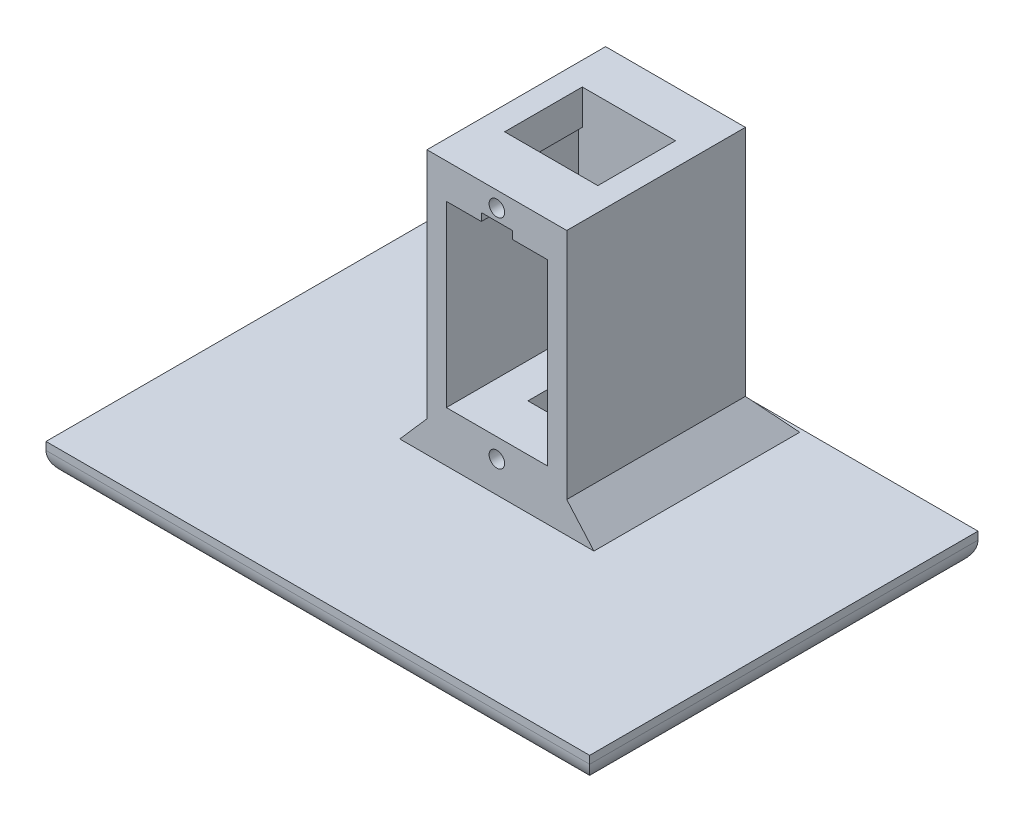
SolidWorks part; units mm, degrees
note: '?' marks a value the reader was unsure of.
ref_plane "Front Plane" through (0, 0, 0) normal (0, 0, 1) x (1, 0, 0)
ref_plane "Top Plane" through (0, 0, 0) normal (0, 1, 0) x (1, 0, 0)
ref_plane "Right Plane" through (0, 0, 0) normal (1, 0, 0) x (0, 0, -1)
sketch "Sketch1" plane through (0, -109.5426, 0) normal (0, -1, 0) x (1, 0, 0)
  line L0 (5.4838, -24.3761) -> (5.4838, -44.3761)
  line L1 (5.4838, -44.3761) -> (23.4838, -44.3761)
  line L2 (8.4838, -24.3761) -> (20.4838, -24.3761)
  line L3 (8.4838, -24.3761) -> (8.4838, -41.3761)
  line L4 (8.4838, -41.3761) -> (20.4838, -41.3761)
  line L5 (20.4838, -24.3761) -> (20.4838, -41.3761)
  line L6 (23.4838, -24.3761) -> (23.4838, -44.3761)
  line L7 (5.4838, -24.3761) -> (8.4838, -24.3761)
  line L8 (23.4838, -24.3761) -> (20.4838, -24.3761)
  line M6 (8.4838, -24.3761) -> (8.4838, -41.3761)
  line M7 (8.4838, -41.3761) -> (20.4838, -41.3761)
  line M8 (20.4838, -41.3761) -> (20.4838, -24.3761)
  dimension "D1" = 3
extrude "Boss-Extrude1" add sketch "Sketch1" against normal up to vertex (22 mm away) contours L6 L8 L7 L0 L1 M8 M7 M6
sketch "Sketch2" plane through (0, -109.5426, 0) normal (0, -1, 0) x (1, 0, 0)
  line L0 (23.4838, -24.3761) -> (23.4838, -44.3761) construction
  line L1 (5.4838, -24.3761) -> (23.4838, -24.3761)
  line L2 (5.4838, -24.3761) -> (5.4838, -44.3761)
  line L3 (5.4838, -44.3761) -> (23.4838, -44.3761)
  line L4 (23.4838, -24.3761) -> (23.4838, -44.3761)
extrude "Boss-Extrude2" add sketch "Sketch2" along normal blind 7
sketch "Sketch3" plane through (0, -116.5426, 0) normal (0, -1, 0) x (1, 0, 0)
  line L0 (5.4838, -26.3256) -> (23.4838, -26.3256) construction
  line L3 (5.4838, -24.3761) -> (5.4838, -44.3761) construction
  line L4 (23.4838, -44.3761) -> (23.4838, -24.3761) construction
  line L5 (5.4838, -26.3256) -> (5.4838, -24.3761) construction
  line L7 (-20.5162, -51.3256) -> (49.4838, -51.3256)
  line L8 (-20.5162, -51.3256) -> (-20.5162, -1.3256)
  line L9 (-20.5162, -1.3256) -> (49.4838, -1.3256)
  line L10 (49.4838, -51.3256) -> (49.4838, -1.3256)
  line L11 (14.4838, -1.3256) -> (14.4838, -51.3256) construction
  line L12 (-20.5162, -26.3256) -> (49.4838, -26.3256) construction
  point P12 (14.4838, -26.3256)
  dimension "D1" = 50
  dimension "D2" = 70
  dimension "D3" = 1.9496
  dimension "D4" = 18
extrude "Boss-Extrude3" add sketch "Sketch3" along normal blind 4
sketch "Sketch31" plane through (0, -116.5426, 0) normal (0, 1, 0) x (1, 0, 0)
  line L0 (23.4838, 44.3761) -> (23.4838, 47.3761) construction
  line L2 (5.4838, 44.3761) -> (23.4838, 44.3761)
  line L3 (5.4838, 44.3761) -> (5.4838, 47.3761)
  line L4 (5.4838, 47.3761) -> (23.4838, 47.3761)
  line L5 (23.4838, 44.3761) -> (23.4838, 47.3761)
  dimension "D1" = 3
  dimension "D4" = 18
extrude "Boss-Extrude7" add sketch "Sketch31" along normal blind 34
sketch "Sketch4" plane through (0, 0, -51.3256) normal (0, 0, -1) x (-1, 0, 0)
  line L0 (-49.4838, -117.5426) -> (-49.4838, -120.5426)
  line L1 (-49.4838, -116.5426) -> (20.5162, -116.5426) construction
  line L2 (-49.4838, -116.5426) -> (-49.4838, -117.5426) construction
  line L3 (-46.4838, -120.5426) -> (17.5162, -120.5426) construction
  line L4 (20.5162, -116.5426) -> (20.5162, -117.5426) construction
  line L5 (-49.4838, -120.5426) -> (-46.4838, -120.5426)
  line L6 (17.5162, -120.5426) -> (20.5162, -120.5426)
  line L7 (20.5162, -120.5426) -> (20.5162, -117.5426)
  arc A0 (-49.4838, -117.5426) -> (-46.4838, -120.5426) centre (-46.4838, -117.5426) ccw
  arc A1 (20.5162, -117.5426) -> (17.5162, -120.5426) centre (17.5162, -117.5426) cw
  point P10 (20.5162, -120.5426)
  dimension "D1" = 3
  dimension "D2" = 3
extrude "Cut-Extrude1" cut sketch "Sketch4" against normal up to next
sketch "Sketch6" plane through (-20.5162, 0, 0) normal (-1, 0, 0) x (0, 0, 1)
  line L0 (-1.3256, -120.5426) -> (-1.3256, -117.5426) construction
  line L1 (-51.3256, -116.5426) -> (-1.3256, -116.5426) construction
  line L2 (-51.3256, -116.5426) -> (-51.3256, -117.5426) construction
  line L3 (-48.3256, -120.5426) -> (-4.3256, -120.5426) construction
  line L4 (-1.3256, -116.5426) -> (-1.3256, -117.5426) construction
  line L5 (-1.3256, -120.5426) -> (-51.3256, -120.5426) construction
  line L6 (-4.3256, -117.5426) -> (-4.3256, -116.5426) construction
  line L7 (-4.3256, -116.5426) -> (-1.3256, -116.5426) construction
  arc A0 (-4.3256, -120.5426) -> (-1.3256, -117.5426) centre (-4.3256, -117.5426) ccw
  arc A1 (-51.3256, -117.5426) -> (-48.3256, -120.5426) centre (-48.3256, -117.5426) ccw
  point P11 (-1.3256, -120.5426)
  dimension "D1" = 3
  dimension "D2" = 1
extrude "Cut-Extrude-Thin1" cut sketch "Sketch6" against normal up to next thin
sketch "Sketch7" plane through (0, -116.5426, 0) normal (0, 1, 0) x (1, 0, 0)
  line L0 (23.4838, 24.3761) -> (23.4838, 44.3761) construction
  line L1 (5.4838, 47.3761) -> (23.4838, 47.3761)
  line L2 (5.4838, 47.3761) -> (5.4838, 24.3761)
  line L3 (5.4838, 24.3761) -> (23.4838, 24.3761)
  line L4 (23.4838, 47.3761) -> (23.4838, 24.3761)
  line L5 (1.9838, 50.8761) -> (1.9838, 20.8761)
  line L6 (1.9838, 20.8761) -> (26.9838, 20.8761)
  line L7 (26.9838, 50.8761) -> (26.9838, 20.8761)
  line L8 (1.9838, 50.8761) -> (26.9838, 50.8761)
  dimension "D1" = 23
  dimension "D2" = 3.5
ref_plane "Plane1" through (0, -112.5426, 0) normal (0, 1, 0) x (1, 0, 0)
sketch "Sketch8" plane through (0, -112.5426, 0) normal (0, 1, 0) x (1, 0, 0)
  line L1 (23.4838, 47.3761) -> (23.4838, 24.3761) construction
  line L2 (5.4838, 24.3761) -> (23.4838, 24.3761) construction
  line L3 (5.4838, 47.3761) -> (5.4838, 24.3761) construction
  line L4 (5.4838, 47.3761) -> (23.4838, 47.3761)
  line L5 (23.4838, 47.3761) -> (23.4838, 24.3761)
  line L6 (5.4838, 24.3761) -> (23.4838, 24.3761)
  line L7 (5.4838, 47.3761) -> (5.4838, 24.3761)
  dimension "D1" = 23
  dimension "D2" = 18
loft "Loft2" add profiles "Sketch8" section "Sketch7" section "Sketch8"
sketch "Sketch9" plane through (5.4838, 0, 0) normal (-1, 0, 0) x (0, 0, 1)
  line L0 (-24.3761, -112.5426) -> (-24.3761, -116.5426)
  line L1 (-1.3256, -116.5426) -> (-51.3256, -116.5426) construction
  line L2 (-24.3761, -116.5426) -> (-20.8761, -116.5426)
  line L3 (-20.8761, -116.5426) -> (-24.3761, -112.5426) construction
  line L4 (-20.8761, -116.5426) -> (-24.3761, -112.5426)
  dimension "D1" = 3.5
  dimension "D2" = 4
extrude "Cut-Extrude2" cut sketch "Sketch9" against normal through all both and the other way through all
sketch "Sketch10" plane through (0, 0, -24.3761) normal (0, 0, 1) x (1, 0, 0)
  circle A0 centre (14.4838, -112.5426) radius 1
  dimension "D1" = 2
extrude "Cut-Extrude3" cut sketch "Sketch10" against normal blind 10
sketch "Sketch11" plane through (0, 0, -24.3761) normal (0, 0, 1) x (1, 0, 0)
  line L0 (20.4838, -109.5426) -> (8.4838, -109.5426) construction
  line L1 (12.4838, -114.5426) -> (16.4838, -114.5426)
  line L2 (12.4838, -114.5426) -> (12.4838, -109.5426)
  line L3 (12.4838, -109.5426) -> (16.4838, -109.5426)
  line L4 (16.4838, -114.5426) -> (16.4838, -109.5426)
  line L5 (14.4838, -109.5426) -> (14.4838, -114.5426) construction
  point P0 (14.4838, -112.5426)
  dimension "D1" = 5
  dimension "D2" = 4
ref_plane "Plane2" through (0, 0, -34.3761) normal (0, 0, 1) x (1, 0, 0)
sketch "Sketch12" plane through (0, 0, -34.3761) normal (0, 0, 1) x (1, 0, 0)
  line L0 (12.4838, -114.5426) -> (16.4838, -114.5426) construction
  line L1 (14.4838, -109.5426) -> (14.4838, -114.5426) construction
  line L2 (12.4838, -114.5426) -> (12.4838, -109.5426) construction
  line L3 (12.4838, -109.5426) -> (16.4838, -109.5426) construction
  line L4 (16.4838, -114.5426) -> (16.4838, -109.5426) construction
  line L5 (12.4838, -114.5426) -> (16.4838, -114.5426)
  line L6 (14.4838, -109.5426) -> (14.4838, -114.5426) construction
  line L7 (12.4838, -114.5426) -> (12.4838, -109.5426)
  line L8 (12.4838, -109.5426) -> (16.4838, -109.5426)
  line L9 (16.4838, -114.5426) -> (16.4838, -109.5426)
extrude "Cut-Extrude4" cut sketch "Sketch12" along normal blind 4
sketch "Sketch13" plane through (0, -87.5426, 0) normal (0, 1, 0) x (1, 0, 0)
  line L2 (5.4838, 47.3761) -> (23.4838, 47.3761)
  line L3 (5.4838, 47.3761) -> (5.4838, 24.3761)
  line L4 (5.4838, 24.3761) -> (23.4838, 24.3761)
  line L5 (23.4838, 47.3761) -> (23.4838, 24.3761)
extrude "Boss-Extrude4" add sketch "Sketch13" along normal blind 5
sketch "Sketch14" plane through (0, 0, -24.3761) normal (0, 0, 1) x (1, 0, 0)
  circle A0 centre (14.4838, -84.5426) radius 1
  dimension "D1" = 2
extrude "Cut-Extrude5" cut sketch "Sketch14" against normal blind 10
sketch "Sketch16" plane through (0, -82.5426, 0) normal (0, 1, 0) x (1, 0, 0)
  line L2 (5.4838, 41.3761) -> (23.4838, 41.3761) construction
  line L3 (5.4838, 47.3761) -> (5.4838, 24.3761) construction
  line L4 (23.4838, 24.3761) -> (23.4838, 47.3761) construction
  line L5 (14.4838, 41.3761) -> (8.4838, 41.3761)
  line L6 (8.4838, 41.3761) -> (8.4838, 31.3761)
  line L7 (8.4838, 31.3761) -> (20.4838, 31.3761)
  line L8 (20.4838, 31.3761) -> (20.4838, 41.3761)
  line L9 (20.4838, 41.3761) -> (14.4838, 41.3761)
  line L10 (23.4838, 41.3761) -> (20.4838, 41.3761) construction
  line L11 (14.4838, 24.3761) -> (14.4838, 31.3761) construction
  line L12 (5.4838, 24.3761) -> (23.4838, 24.3761) construction
  dimension "D1" = 7
  dimension "D2" = 12
  dimension "D3" = 10
  dimension "D4" = 6
extrude "Cut-Extrude6" cut sketch "Sketch16" against normal up to next
sketch "Sketch29" plane through (0, 0, -24.3761) normal (0, 0, 1) x (1, 0, 0)
  line L0 (7.9838, -87.0426) -> (7.9838, -110.0426)
  line L1 (8.4838, -87.5426) -> (20.4838, -87.5426) construction
  line L2 (8.4838, -87.5426) -> (8.4838, -109.5426) construction
  line L3 (8.4838, -109.5426) -> (20.4838, -109.5426) construction
  line L4 (20.4838, -87.5426) -> (20.4838, -109.5426) construction
  line L5 (7.9838, -110.0426) -> (20.9838, -110.0426)
  line L6 (20.9838, -87.0426) -> (20.9838, -110.0426)
  line L7 (7.9838, -87.0426) -> (20.9838, -87.0426)
  dimension "D1" = 0.5
extrude "Cut-Extrude10" cut sketch "Sketch29" against normal up to vertex
sketch "Sketch18" plane through (5.4838, 0, 0) normal (-1, 0, 0) x (0, 0, 1)
  line L2 (-26.3256, -31.6531) -> (-26.3256, -12.9944) construction
  line L3 (-51.3256, -116.5426) -> (-1.3256, -116.5426) construction
  point P10 (-26.3256, -116.5426)
  dimension "D1" = 50
sketch "Sketch30" plane through (0, 0, -24.3761) normal (0, 0, 1) x (1, 0, 0)
  line L0 (14.4838, -87.0426) -> (14.4838, -86.0426) construction
  line L1 (20.9838, -87.0426) -> (7.9838, -87.0426) construction
  line L3 (12.4838, -86.0426) -> (16.4838, -86.0426)
  line L4 (12.4838, -86.0426) -> (12.4838, -87.0426)
  line L5 (12.4838, -87.0426) -> (16.4838, -87.0426)
  line L6 (16.4838, -86.0426) -> (16.4838, -87.0426)
  line L7 (12.4838, -86.0426) -> (16.4838, -87.0426) construction
  line L8 (12.4838, -87.0426) -> (16.4838, -86.0426) construction
  point P5 (14.4838, -86.5426)
  dimension "D1" = 1
  dimension "D2" = 4
extrude "Cut-Extrude11" cut sketch "Sketch30" against normal blind 7
ref_plane "Plane3" through (0, 0, -26.3256) normal (0, 0, 1) x (1, 0, 0)
sketch "Sketch19" plane through (0, 0, -26.3256) normal (0, 0, 1) x (1, 0, 0)
  line L1 (5.4838, -82.5426) -> (23.4838, -82.5426)
  line L2 (5.4838, -82.5426) -> (5.4838, -112.5426)
  line L3 (5.4838, -112.5426) -> (23.4838, -112.5426)
  line L4 (23.4838, -82.5426) -> (23.4838, -112.5426)
  dimension "D1" = 18
  dimension "D2" = 30
ref_plane "Plane4" through (0, 0, -30.9979) normal (0, 0, 1) x (1, 0, 0)
ref_plane "Plane5" through (0, 0, -8.3761) normal (0, 0, 1) x (1, 0, 0)
sketch "Sketch21" plane through (0, 0, -41.3761) normal (0, 0, 1) x (1, 0, 0)
  line L0 (14.4838, -82.5426) -> (14.4838, -93.5426) construction
  line L1 (5.4838, -82.5426) -> (23.4838, -82.5426) construction
  line L2 (14.4838, -93.5426) -> (23.4838, -93.5426) construction
  line L3 (23.4838, -82.5426) -> (23.4838, -112.5426) construction
  circle A0 centre (14.4838, -93.5426) radius 5
  dimension "D1" = 10
  dimension "D2" = 9
  dimension "D3" = 11
extrude "Cut-Extrude12" cut sketch "Sketch21" against normal blind 6
sketch "Sketch32" plane through (0, 0, -41.3761) normal (0, 0, 1) x (1, 0, 0)
  circle A0 centre (14.4838, -93.5426) radius 5
extrude "Boss-Extrude8" add sketch "Sketch32" against normal blind 2
sketch "Sketch33" plane through (0, 0, -43.3761) normal (0, 0, -1) x (-1, 0, 0)
  circle A0 centre (-14.4838, -93.5426) radius 1.5
  dimension "D1" = 3
extrude "Cut-Extrude13" cut sketch "Sketch33" against normal up to next
ref_plane "Plane6" through (0, 0, -28.2597) normal (0, 0, 1) x (1, 0, 0)
ref_plane "Plane7" through (0, 0, 0.6239) normal (0, 0, 1) x (1, 0, 0)
ref_point "Point1"
ref_axis "Axis1" through (14.4838, -93.5426, -105.1184) along (0, 0, 1)?
ref_point "Point2"
sketch "Sketch34" plane through (0, 0, -41.3761) normal (0, 0, 1) x (1, 0, 0)
  circle A0 centre (14.4838, -93.5426) radius 2.5
  dimension "D1" = 5
extrude "Cut-Extrude14" cut sketch "Sketch34" against normal blind 1
